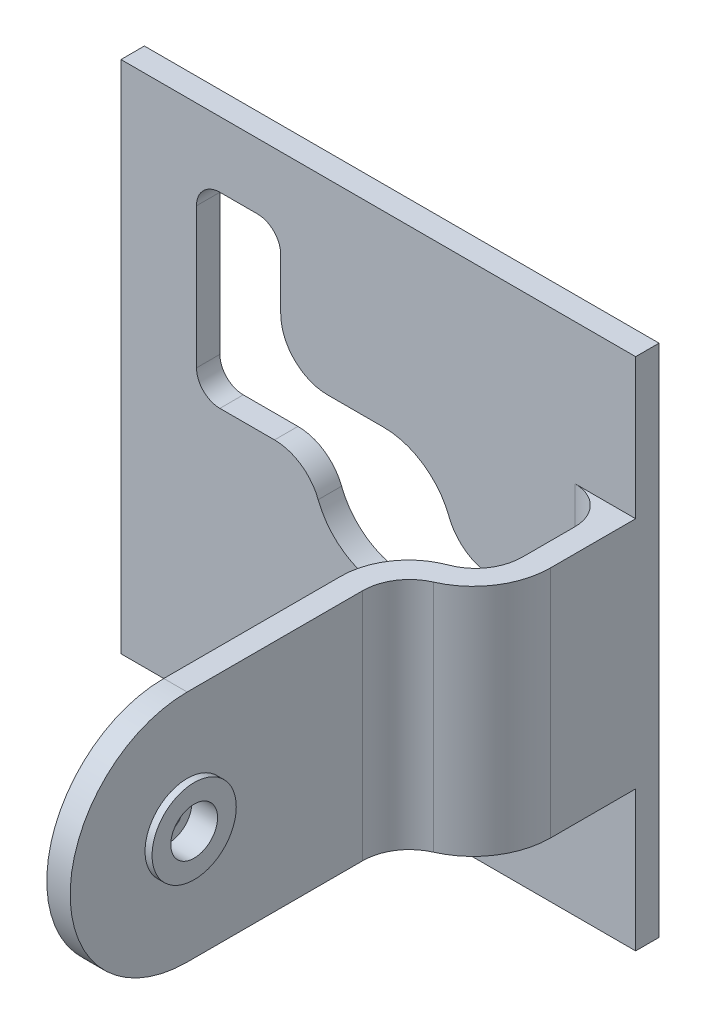
SolidWorks part; units mm, degrees
ref_plane "Front Plane" through (0, 0, 0) normal (0, 0, 1) x (1, 0, 0)
ref_plane "Top Plane" through (0, 0, 0) normal (0, 1, 0) x (1, 0, 0)
ref_plane "Right Plane" through (0, 0, 0) normal (1, 0, 0) x (0, 0, -1)
sketch "Sketch1" plane through (0, 0, 0) normal (1, 0, 0) x (0, 0, -1)
  line L1 (0, 12.5) -> (42.5, 12.5)
  line L2 (0, 1.5) -> (0, -12.5)
  line L3 (0, -12.5) -> (42.5, -12.5)
  line L4 (42.5, 12.5) -> (42.5, -12.5)
  circle A0 centre (0, 0) radius 1.5
  circle A1 centre (0, 0) radius 12.5 construction
  arc A2 (0, 12.5) -> (0, -12.5) centre (0, 0) ccw
  dimension "D1" = 3
  dimension "D2" = 25
  dimension "D3" = 42.5
extrude "Boss-Extrude1" add sketch "Sketch1" along normal blind 2.5 contours L1 A2 A0 L3 L4 region at (0, 0, -16.3553)
sketch "Sketch2" plane through (0, 0, 0) normal (-1, 0, 0) x (0, 0, 1)
  circle A0 centre (0, 0) radius 1.5
  circle A1 centre (0, 0) radius 4.5
  dimension "D1" = 9
  dimension "D2" = 3
extrude "Boss-Extrude2" add sketch "Sketch2" along normal blind 1.8 and the other way offset from surface 0.75 other way up to face at (2.5, 0, -18.125)
sketch "Sketch4" plane through (2.5, 0, 0) normal (1, 0, 0) x (0, 0, -1)
  circle A0 centre (0, 0) radius 2.5
extrude "Cut-Extrude1" cut sketch "Sketch4" against normal blind 2
sketch "Sketch5" plane through (2.5, 0, 0) normal (1, 0, 0) x (0, 0, -1)
  circle A0 centre (0, 0) radius 4.5
  circle A1 centre (0, 0) radius 2.5
  dimension "D1" = 9
  dimension "D2" = 5
extrude "Boss-Extrude3" add sketch "Sketch5" along normal blind 0.75
sketch "Sketch6" plane through (0, 0, -42.5) normal (0, 0, -1) x (-1, 0, 0)
  line L1 (-0.0625, 27.5) -> (44.5716, 27.5)
  line L3 (-2.5, -27.5) -> (44.5716, -27.5)
  line L4 (44.5716, 27.5) -> (44.5716, -27.5)
  line L6 (44.5716, -27.5) -> (-10.4284, 27.5) construction
  line L7 (-2.5, -27.5) -> (-10.4284, -27.5)
  line L9 (-0.0625, 27.5) -> (-10.4284, 27.5)
  line L10 (-10.4284, -27.5) -> (-10.4284, 27.5)
  line L11 (44.5716, 27.5) -> (-10.4284, -27.5) construction
  point P4 (17.0716, 0)
  dimension "D1" = 55
  dimension "D2" = 55
extrude "Boss-Extrude4" add sketch "Sketch6" against normal blind 2.5
ref_plane "Plane1" through (-16.5, 0, 0) normal (1, 0, 0) x (0, 0, -1)
ref_plane "Plane2" through (10.05, 0, 0) normal (1, 0, 0) x (0, 0, -1)
sketch "Sketch7" plane through (0, 0, -40) normal (0, 0, 1) x (1, 0, 0)
  line L1 (-36.5, 12.5144) -> (-36.5, 17.9994)
  line L2 (-27.5, 12.5144) -> (-27.5, 17.9994)
  line L3 (-30, 20.4994) -> (-34, 20.4994)
  line L13 (-22.5, 7.5) -> (-16.5, 7.5)
  line L14 (-28.1619, 0.5) -> (-34, 0.5)
  line L17 (-36.5, 3) -> (-36.5, 12.5144)
  arc A2 (-36.5, 17.9994) -> (-34, 20.4994) centre (-34, 17.9994) cw
  arc A3 (-27.5, 17.9994) -> (-30, 20.4994) centre (-30, 17.9994) ccw
  arc A6 (-23.4971, -2.7) -> (-28.1619, 0.5) centre (-28.1619, -4.5) ccw
  arc A7 (-23.4971, -2.7) -> (-16.5, 7.5) centre (-16.5, 0) ccw
  arc A8 (-27.5, 12.5144) -> (-22.5, 7.5) centre (-22.5, 12.5) ccw
  arc A11 (-36.5, 3) -> (-34, 0.5) centre (-34, 3) ccw
  point P16 (0, 0)
extrude "Cut-Extrude2" cut sketch "Sketch7" against normal up to next
sketch "Sketch8" plane through (0, 0, 0) normal (0, 1, 0) x (1, 0, 0)
  line L1 (10.4284, 40) -> (7.9284, 40)
  line L2 (10.4284, 40) -> (10.4284, 30.9168)
  line L4 (7.9284, 40) -> (7.9284, 30.385)
  line L5 (0, 0) -> (0, 40) construction
  line L10 (2.5, 0) -> (2.5, 40) construction
  line L12 (0, 18.9371) -> (0, 9.0717)
  line L13 (0, 9.0717) -> (2.5, 9.0717)
  line L14 (2.5, 18.7594) -> (2.5, 9.0717)
  arc A0 (7.9284, 30.385) -> (4.6868, 25.7044) centre (2.9284, 30.385) cw
  arc A1 (5.4839, 23.3349) -> (2.5, 18.7594) centre (7.5, 18.7594) ccw
  arc A3 (5.4839, 23.3349) -> (10.4284, 30.9168) centre (2.1431, 30.9168) ccw
  arc A4 (4.6868, 25.7044) -> (0, 18.9371) centre (7.2291, 18.9371) ccw
  point P2 (4.5633, 24.7588)
  point P5 (-1.4118, 20.6413)
  point P9 (-1.8607, 18.7838)
  point P21 (0, 24.8672)
  point P23 (2.9284, 24.8672)
  point P24 (4.6717, 24.7743)
  point P25 (0, 18.2575)
  point P26 (7.9284, 30.385)
  point P27 (10.4284, 30.9168)
  dimension "D3" = 5
  dimension "D1" = 2.5
  dimension "D2" = 2.5
sketch "Sketch9" plane through (0, -12.5, 0) normal (0, -1, 0) x (1, 0, 0)
  line L0 (2.5, 0) -> (2.5, -40) construction
  line L1 (0, -40) -> (2.5, -40)
  line L2 (0, -40) -> (0, -9.5612)
  line L3 (0, -9.5612) -> (2.5, -9.5612)
  line L4 (2.5, -40) -> (2.5, -9.5612)
extrude "Cut-Extrude3" cut sketch "Sketch9" against normal up to next
extrude "Boss-Extrude5" add sketch "Sketch8" along normal mid plane 25
fillet "Fillet1" radius 4 1 edges at (7.9284, 0, -40)
pattern_circular "CirPattern1" count 2 every 180 about axis through (-16.5, 0, -40) along (0, 0, 1) of "Cut-Extrude2"
